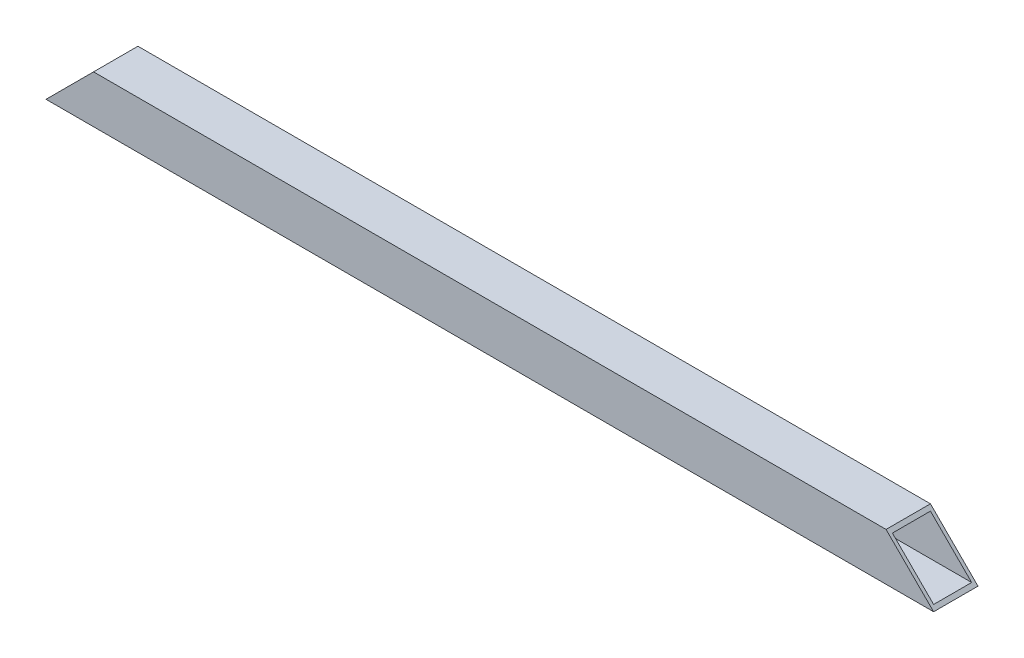
SolidWorks part; units mm, degrees
ref_plane "Спереди" through (0, 0, 0) normal (0, 0, 1) x (1, 0, 0)
ref_plane "Сверху" through (0, 0, 0) normal (0, 1, 0) x (1, 0, 0)
ref_plane "Справа" through (0, 0, 0) normal (1, 0, 0) x (0, 0, -1)
sketch "Эскиз2" plane through (0, 0, 0) normal (1, 0, 0) x (0, 0, -1)
  line L1 (-35, 37.5) -> (35, 37.5)
  line L2 (-35, 37.5) -> (-35, -37.5)
  line L3 (-35, -37.5) -> (35, -37.5)
  line L4 (35, 37.5) -> (35, -37.5)
  line L5 (-35, 37.5) -> (35, -37.5) construction
  line L6 (-35, -37.5) -> (35, 37.5) construction
  point P0 (0, 0)
extrude "Вытянуть-Тонкостенный1" add sketch "Эскиз2" along normal blind 1400 thin thin type one direction reverse wall 5
sketch "Эскиз3" plane through (0, 0, -35) normal (0, 0, -1) x (-1, 0, 0)
  line L0 (-1400, -37.5) -> (-1325, 37.5)
  line L1 (-1400, 37.5) -> (0, 37.5) construction
  line L2 (-1325, 37.5) -> (-75, 37.5)
  line L3 (-75, 37.5) -> (0, -37.5)
  line L4 (0, -37.5) -> (-1400, -37.5)
extrude "Вырез-Вытянуть1" cut sketch "Эскиз3" against normal through all flip side to cut
